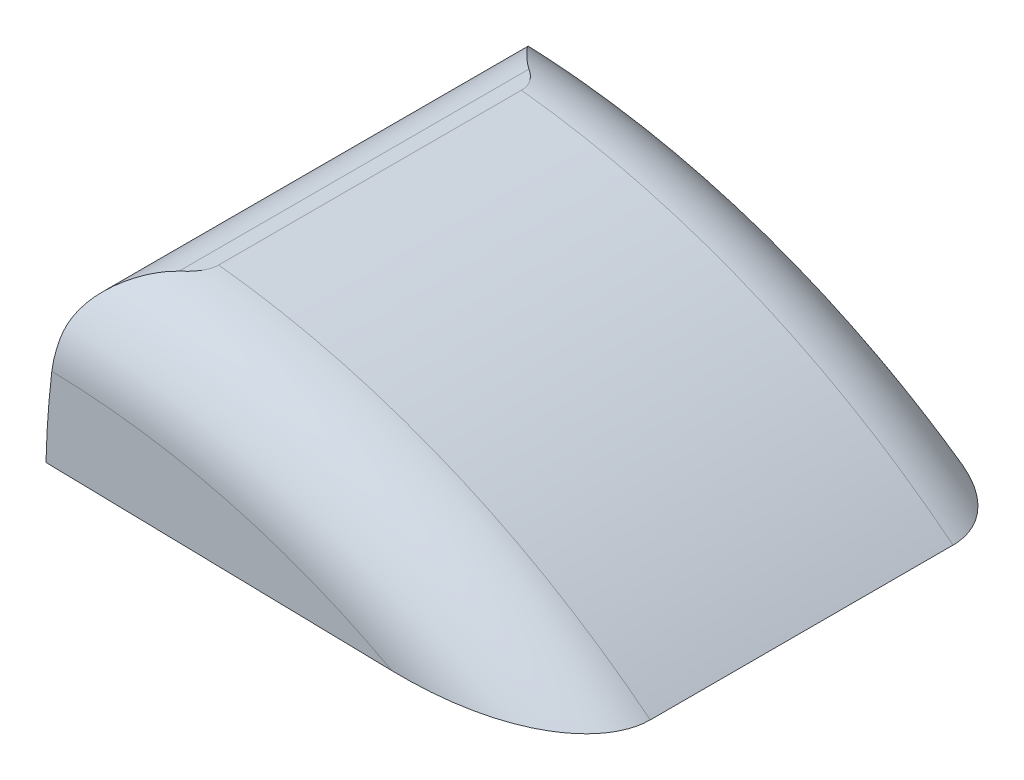
SolidWorks part; units mm, degrees
ref_plane "Front Plane" through (0, 0, 0) normal (0, 0, 1) x (1, 0, 0)
ref_plane "Top Plane" through (0, 0, 0) normal (0, 1, 0) x (1, 0, 0)
ref_plane "Right Plane" through (0, 0, 0) normal (1, 0, 0) x (0, 0, -1)
sketch "Sketch1" plane through (0, 3.6477, 0) normal (0, 0, 1) x (1, 0, 0)
  line L0 (-77.17, -23.8173) -> (-4.7338, -25.3585)
  line L3 (-65.5452, -0.2617) -> (-74.3585, -1.1182)
  line L8 (-74.3585, -1.1182) -> (-75.8, -8.2341)
  arc A0 (-77.17, -23.8173) -> (-75.8, -8.2341) centre (43.526, -26.5761) cw
  arc A2 (-65.5452, -0.2617) -> (-4.7338, -25.3585) centre (-78.3459, -117.5026) cw
extrude "Boss-Extrude1" add sketch "Sketch1" against normal blind 68.0589
fillet "Fillet9" radius 12.7 1 edges at (-33.3542, -4.8364, 0)
fillet "Fillet10" radius 12.7 1 edges at (-33.3542, -4.8364, -68.0589)
shell "Shell2" thickness 2.54 removed face at (-33.6441, -21.0956, -34.1299)
fillet "Fillet16" radius 8.89 1 edges at (-74.3585, 2.5295, -34.0295)
